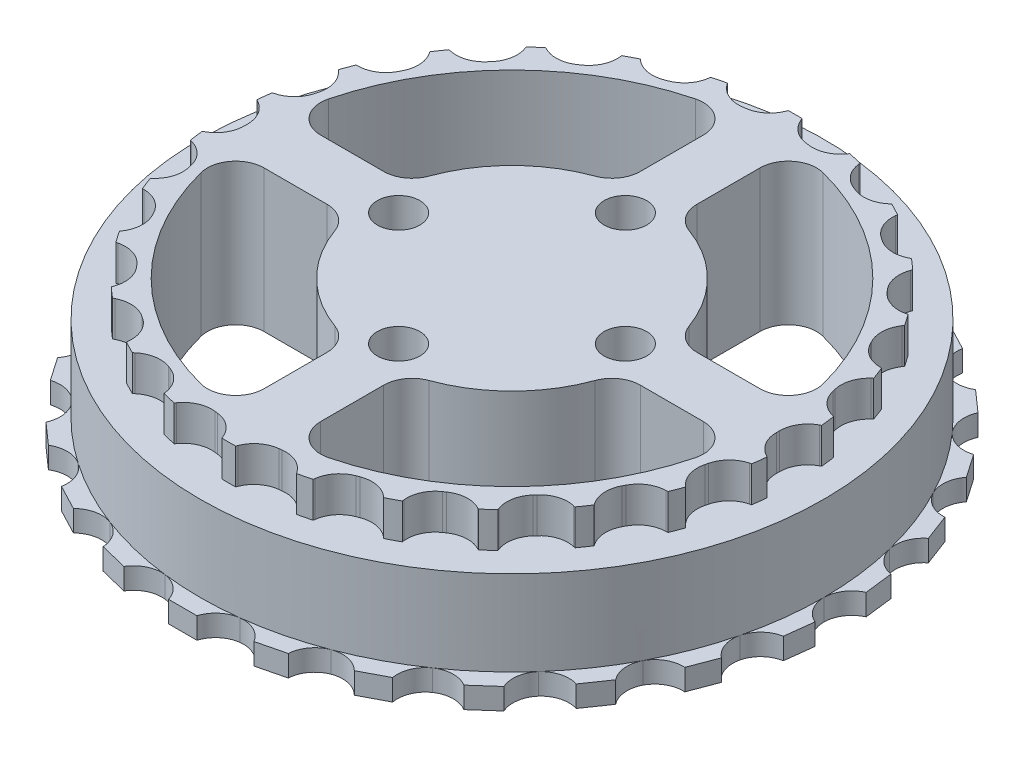
SolidWorks part; units mm, degrees
note: '?' marks a value the reader was unsure of.
ref_plane "Front Plane" through (0, 0, 0) normal (0, 0, 1) x (1, 0, 0)
ref_plane "Top Plane" through (0, 0, 0) normal (0, 1, 0) x (1, 0, 0)
ref_plane "Right Plane" through (0, 0, 0) normal (1, 0, 0) x (0, 0, -1)
ref_axis "Axis1" through (0, 10.5, 0) along (0, -1, 0)?
sketch "Sketch1" plane through (0, 0, 0) normal (0, 1, 0) x (1, 0, 0)
  line L0 (0, 22) -> (0, -22) construction
  line L1 (-22, 0) -> (22, 0) construction
  line L2 (-2, 22) -> (-2, -22)
  line L3 (2, 22) -> (2, -22)
  line L4 (-22, -2) -> (22, -2)
  line L5 (-22, 2) -> (22, 2)
  circle A0 centre (0, 0) radius 22
  circle A1 centre (0, 0) radius 9.75
  circle A2 centre (0, 0) radius 18
  dimension "D1" = 44
  dimension "D2" = 19.5
  dimension "D7" = 4
  dimension "D3" = 2
  dimension "D4" = 2
  dimension "D5" = 2
  dimension "D6" = 2
extrude "Boss-Extrude1" add sketch "Sketch1" along normal blind 10 contours A2 L3 A0 L4 | A2 L2 A0 L3 | A2 L4 A0 L2 | A2 L5 A0 L4 | A2 L2 A0 L5 | A2 L3 A0 L2 | A2 L5 A0 L3 | A2 L4 A0 L5 | L3 A2 L2 A1 | L4 A1 L5 L3 | L2 A1 L3 L4 | L2 A2 L3 A1 | L4 A2 L5 A1 | L3 A1 L4 | L4 A1 L2 | L5 A1 L4 L2 | L5 A2 L4 A1 | L3 A1 L2 L5 | L5 L2 L4 L3 | L5 A1 L3 | L2 A1 L5
fillet "Fillet1" radius 2 16 edges at (-2, 5, 17.8885) (-2, 5, -17.8885) (17.8885, 5, -2) (-17.8885, 5, -2) (9.5427, 5, -2) (-9.5427, 5, -2) (-2, 5, 9.5427) (-2, 5, -9.5427) (2, 5, 9.5427) (2, 5, -9.5427) (2, 5, 17.8885) (2, 5, -17.8885) (17.8885, 5, 2) (-17.8885, 5, 2) (9.5427, 5, 2) (-9.5427, 5, 2)
sketch "Sketch2" plane through (0, 0, 0) normal (0, -1, 0) x (1, 0, 0)
  line L0 (0, 0) -> (0, 22) construction
  line L1 (0, 23.2273) -> (0, 21.9773) construction
  line L2 (-1, 23.2273) -> (1, 23.2273)
  line L3 (-1, 23.2273) -> (-1, 21.9773)
  line L4 (-1, 21.9773) -> (1, 21.9773)
  line L5 (1, 23.2273) -> (1, 21.9773)
  circle A1 centre (0, 0) radius 22 construction
  circle A2 centre (0, 0) radius 22
  point P10 (0, 0)
  circle M9 centre (0, 0) radius 22
  dimension "D1" = 1.25
  dimension "D2" = 2
extrude "Boss-Extrude2" add sketch "Sketch2" against normal blind 1.5 contours L5 L2 L3 M9
fillet "Fillet2" radius 2 2 edges at (-1, 0.75, 21.9773) (1, 0.75, 21.9773)
pattern_circular "CirPattern1" count 26 over 360 about axis through (0, 0, 0) along (0, 1, 0) of "Boss-Extrude2", "Fillet2"
sketch "Sketch3" plane through (0, 10, 0) normal (0, 1, 0) x (1, 0, 0)
  line L0 (0, 0) -> (0, 23.2273) construction
  line L1 (0, 0) -> (5.5586, 22.5523) construction
  line L4 (1, 23.2273) -> (-1, 23.2273) construction
  line L5 (6.5296, 22.313) -> (4.5877, 22.7916) construction
  line L6 (4.2993, 19.5324) -> (3.5098, 18.4186)
  line L7 (2.6368, 21.8414) -> (0, 0) construction
  line L8 (0.4726, 19.9944) -> (0.9743, 18.7247)
  line L9 (0, 22) -> (0, 20)
  line L10 (4.7863, 19.4188) -> (5.2649, 21.3607)
  circle A2 centre (0, 0) radius 22
  circle A3 centre (0, 0) radius 22 construction
  circle A4 centre (0, 0) radius 20
  circle A5 centre (0, 0) radius 18.75
  point P24 (0, 0)
  circle M17 centre (0, 0) radius 22
  dimension "D1" = 2
  dimension "D2" = 3.25
  dimension "D3" = 1
  dimension "D4" = 2
extrude "Cut-Extrude1" cut sketch "Sketch3" against normal blind 2.5 contours A4 L10 L9 M17 | A5 L6 A4 L8
fillet "Fillet3" radius 2 2 edges at (3.5098, 8.75, -18.4186) (0.9743, 8.75, -18.7247)
pattern_circular "CirPattern2" count 26 over 360 about axis through (0, 0, 0) along (0, 1, 0) of "Cut-Extrude1", "Fillet3"
sketch "Sketch4" plane through (0, 10, 0) normal (0, 1, 0) x (1, 0, 0)
  line L0 (0, 22) -> (0, -22) construction
  line L1 (-22.0001, 0) -> (22, 0) construction
  line L2 (-8, 0) -> (0, 0) construction
  line L3 (-8, 1.5) -> (0, 1.5) construction
  line L4 (-1.5, 8) -> (-1.5, 0) construction
  circle A0 centre (0, 0) radius 22 construction
  arc A1 (2.6368, 21.8414) -> (-2.6668, 21.8378) centre (0, 0) ccw construction
  circle A2 centre (0, 8) radius 1.5
  circle A3 centre (0, -8) radius 1.5
  circle A4 centre (-8, 0) radius 1.5
  circle A5 centre (8, 0) radius 1.5
  dimension "D1" = 3
  dimension "D2" = 8
extrude "Cut-Extrude2" cut sketch "Sketch4" against normal blind 2.75
